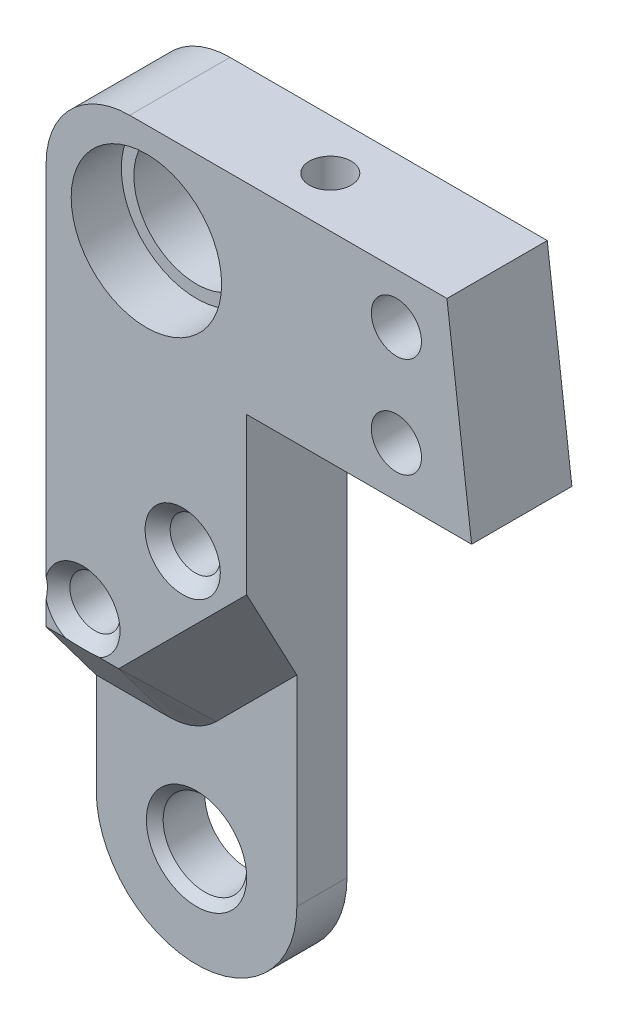
SolidWorks part; units mm, degrees
ref_plane "Plano frontal" through (0, 0, 0) normal (0, 0, 1) x (1, 0, 0)
ref_plane "Plano superior" through (0, 0, 0) normal (0, 1, 0) x (1, 0, 0)
ref_plane "Plano direito" through (0, 0, 0) normal (1, 0, 0) x (0, 0, -1)
sketch "Esboço1" plane through (0, 0, 0) normal (0, 0, 1) x (1, 0, 0)
  line L0 (-6, 6) -> (-6, 39)
  line L1 (0, 0) -> (6, 0) construction
  line L2 (0, 0) -> (0, 46) construction
  line L3 (0, 46) -> (6, 46) construction
  line L4 (6, 0) -> (6, 46) construction
  line L5 (-6, 39) -> (0, 39) construction
  line L6 (6, 25) -> (6, 6)
  line L7 (0, 6) -> (22.4315, 8.7542) construction
  line L8 (6, 25) -> (6, 46) construction
  line L9 (6, 25) -> (-6, 25) construction
  line L11 (0, 46) -> (0, 39) construction
  line L12 (0, 39) -> (18.7178, 39) construction
  line L13 (22.4315, 8.7542) -> (-6071.0356, 49636.0618) construction
  line L14 (17.9811, 45) -> (19.4545, 33)
  line L15 (19.4545, 33) -> (17.9811, 33)
  line L16 (0, 6) -> (6, 6) construction
  line L17 (17.9811, 45) -> (17.9811, 33) construction
  line L18 (17.9811, 33) -> (19.4545, 33) construction
  line L19 (17.9811, 39) -> (0, 39) construction
  line L20 (17.9811, 45) -> (-6, 45) construction
  line L21 (-6, 45) -> (-6, 39) construction
  line L22 (19.4545, 33) -> (6, 33) construction
  line L23 (17.9811, 33) -> (6, 33)
  line L24 (6, 33) -> (6, 25)
  line L25 (17.9811, 45) -> (-1, 45)
  line L26 (-6, 40) -> (-6, 39)
  circle A0 centre (0, 6) radius 6 construction
  circle A1 centre (0, 39) radius 4.5
  arc A2 (-6, 6) -> (0, 0) centre (0, 6) ccw
  arc A3 (0, 0) -> (6, 6) centre (0, 6) ccw
  arc A4 (-6, 40) -> (-1, 45) centre (-1, 40) cw
  dimension "D3" = 12
  dimension "D5" = 9
  dimension "D7" = 22.6
  dimension "D8" = 7
  dimension "D9" = 12
  dimension "D10" = 5
  dimension "D1" = 6
  dimension "D2" = 46
  dimension "D4" = 33
  dimension "D6" = 25
extrude "Ressalto-extrusão1" add sketch "Esboço1" along normal blind 3
sketch "Esboço2" plane through (0, 0, 3) normal (0, 0, 1) x (1, 0, 0)
  line L0 (6, 25) -> (-6, 25) construction
  line L1 (6, 25) -> (-6, 25) construction
  line L2 (6, 25) -> (6, 18)
  line L3 (6, 6) -> (6, 33) construction
  line L4 (6, 18) -> (6, 12) construction
  line L5 (-6, 40) -> (-6, 25)
  line L9 (6, 6) -> (6, 33) construction
  line L10 (6, 6) -> (6, 33) construction
  line L11 (6, 12) -> (-6, 12) construction
  line L14 (-6, 25) -> (-6, 12)
  line L15 (-6, 12) -> (-6, 6) construction
  line L17 (6, 33) -> (19.4545, 33)
  line L18 (6, 33) -> (19.4545, 33)
  line L19 (-6, 12) -> (-1.6569, 12)
  line L20 (1.1716, 13.1716) -> (6, 18)
  line L21 (6, 33) -> (6, 25)
  line L22 (0, 12) -> (0, 6) construction
  line L23 (6, 12) -> (6, 6) construction
  line L24 (6, 6) -> (6, 33)
  line L25 (19.4545, 33) -> (17.9811, 45)
  line L26 (19.4545, 33) -> (17.9811, 45)
  line L27 (17.9811, 45) -> (-1, 45)
  line L28 (17.9811, 45) -> (-1, 45)
  line L29 (-6, 40) -> (-6, 6)
  line L30 (-6, 40) -> (-6, 6) construction
  circle A1 centre (0, 39) radius 4.5 construction
  circle A2 centre (0, 39) radius 4.5
  arc A4 (-1, 45) -> (-6, 40) centre (-1, 40) ccw
  arc A5 (-1, 45) -> (-6, 40) centre (-1, 40) ccw
  arc A6 (-1.6569, 12) -> (1.1716, 13.1716) centre (-1.6569, 16) ccw
  arc A8 (-6, 6) -> (6, 6) centre (0, 6) ccw
  arc A11 (-6, 6) -> (6, 6) centre (0, 6) ccw construction
  dimension "D2" = 6
  dimension "D3" = 4
  dimension "D1" = 7
  dimension "D4" = 0
extrude "Ressalto-extrusão2" add sketch "Esboço2" along normal blind 3
chamfer "Chanfro1" distance 3 distance2 4 3 edges at (3.5858, 15.5858, 6) (-0.1261, 12.3045, 6) (-3.8284, 12, 6) first distance on face at (2.9822, 14.9822, 4.875) first distance on face at (-0.1844, 12.4451, 4.5) first distance on face at (-4.3713, 12, 4.875)
sketch "Esboço3" plane through (0, 45, 0) normal (0, 1, 0) x (1, 0, 0)
  line L0 (-1, -3) -> (8, -3) construction
  line L1 (-1, -6) -> (-1, 0) construction
  dimension "D1" = 9
hole_wizard "Furo roscado de M3x0.51" positions "Esboço5" profile "Esboço4" tap size "M3x0.5" standard "Ansi Metric" end condition up to next
sketch "Esboço5" plane through (0, 45, 0) normal (0, 1, 0) x (1, 0, 0)
  point P0 (8, -3)
sketch "Esboço4" plane through (8, 45, 3) normal (1, 0, 0) x (0, 0, 1)
  line L0 (0, 0) -> (0, 12)
  line L1 (0, 12) -> (1.25, 12)
  line L2 (1.25, 12) -> (1.25, 0)
  line L5 (1.25, 0) -> (0, 0)
  line L11 (0, -6.35) -> (0, 107.95) construction
  dimension "Thru Tap Drill Dia." = 2.5
  dimension "Thru Tap Drill Depth" = 12
cosmetic thread "Rosca de furo1" parameters "D2"=3
sketch "Esboço6" plane through (0, 0, 0) normal (0, 0, -1) x (-1, 0, 0)
  circle A0 centre (0, 39) radius 4.5 construction
  circle A1 centre (0, 39) radius 4.5
  circle A2 centre (0, 39) radius 3.75
  dimension "D1" = 7.5
extrude "Ressalto-extrusão3" add sketch "Esboço6" against normal blind 3
sketch "Esboço7" plane through (0, 0, 0) normal (0, 0, -1) x (-1, 0, 0)
  circle A0 centre (-14.9545, 42) radius 1.25 construction
  circle A1 centre (-14.9545, 36) radius 1.25 construction
  circle A2 centre (-14.9545, 42) radius 1.25 construction
  circle A3 centre (-14.9545, 36) radius 1.25 construction
  circle A4 centre (-14.9545, 42) radius 1.5
  circle A5 centre (-14.9545, 36) radius 1.5
  dimension "D1" = 3
extrude "Corte-extrusão1" cut sketch "Esboço7" against normal up to next
sketch "Esboço8" plane through (0, 0, 6) normal (0, 0, 1) x (1, 0, 0)
  line L0 (-6, 16) -> (-3.8284, 16) construction
  line L1 (2.1716, 24) -> (-3.8284, 24) construction
  line L2 (-3.8284, 18) -> (-3.8284, 16) construction
  line L3 (-6, 16) -> (-1.6569, 16) construction
  line L4 (-3.8284, 24) -> (-3.8284, 18) construction
  circle A0 centre (2.1716, 24) radius 1.5
  circle A1 centre (-3.8284, 18) radius 1.5
  dimension "D1" = 3
  dimension "D2" = 3
  dimension "D3" = 6
  dimension "D4" = 2
  dimension "D5" = 6
extrude "Corte-extrusão2" cut sketch "Esboço8" against normal up to next
chamfer "Chanfro2" distance 0.75 angle 45 2 edges at (-2.3284, 18, 6) (3.6716, 24, 6)
sketch "Esboço14" plane through (0, 0, 0) normal (0, 0, -1) x (-1, 0, 0)
  circle A0 centre (0, 6) radius 2.5
  dimension "D1" = 5
extrude "Corte-extrusão4" cut sketch "Esboço14" against normal up to next
chamfer "Chanfro3" distance 0.5 angle 45 1 edges at (2.5, 6, 3)
sketch "Esboço15" plane through (0, 0, 0) normal (0, 0, -1) x (-1, 0, 0)
  circle A0 centre (-2.1716, 24) radius 1.5 construction
  circle A1 centre (3.8284, 18) radius 1.5 construction
  circle A2 centre (-2.1716, 24) radius 1.5 construction
  circle A3 centre (3.8284, 18) radius 1.5 construction
  circle A4 centre (-2.1716, 24) radius 1.9
  circle A5 centre (3.8284, 18) radius 1.9
  dimension "D1" = 3.8
  dimension "D2" = 3.8
extrude "Corte-extrusão5" cut sketch "Esboço15" against normal blind 1
